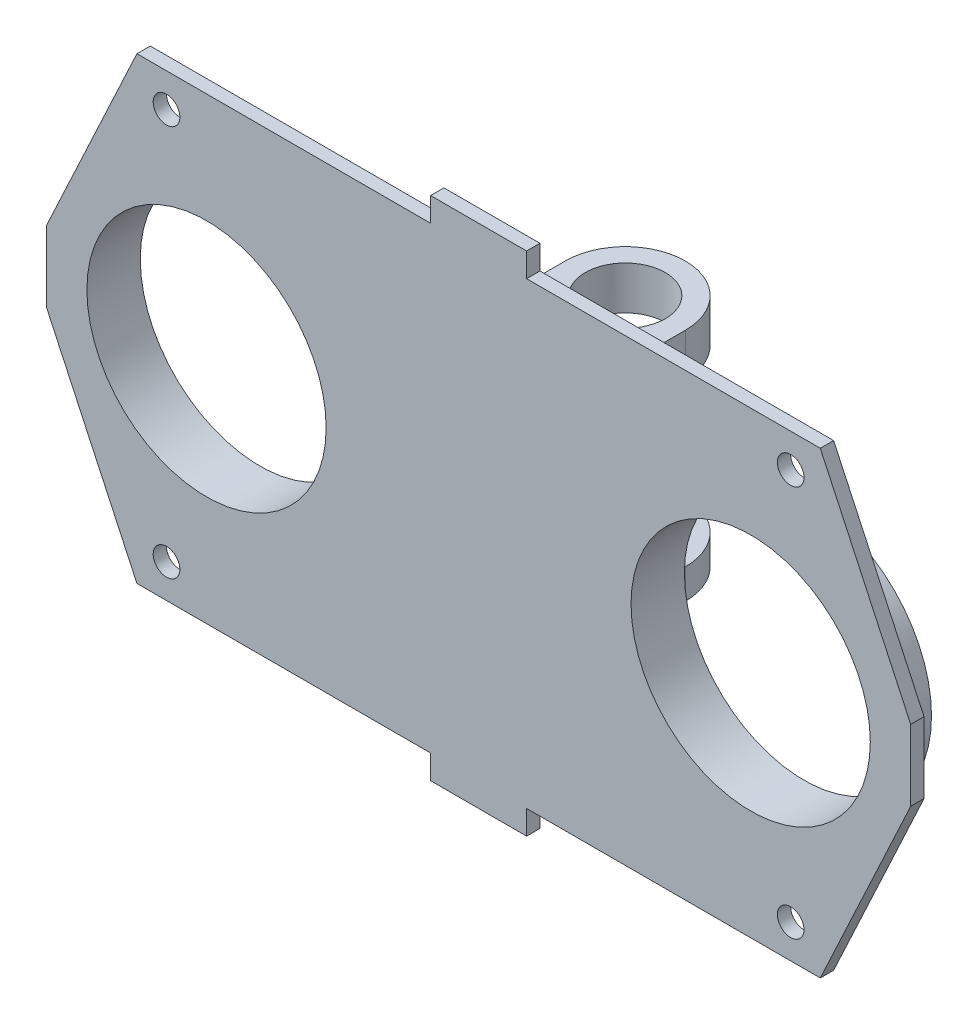
SolidWorks part; units mm, degrees
ref_plane "Front Plane" through (0, 0, 0) normal (0, 0, 1) x (1, 0, 0)
ref_plane "Top Plane" through (0, 0, 0) normal (0, 1, 0) x (1, 0, 0)
ref_plane "Right Plane" through (0, 0, 0) normal (1, 0, 0) x (0, 0, -1)
sketch "Sketch1" plane through (0, 0, 0) normal (0, 0, 1) x (1, 0, 0)
  line L0 (-219, 0) -> (219, 0) construction
  line L1 (0, 136.35) -> (0, -136.35) construction
  line L2 (-128.1, 86) -> (-18, 86)
  line L4 (-128.1, -86) -> (-18, -86)
  line L6 (-128.1, 86) -> (128.1, -86) construction
  line L7 (-128.1, -86) -> (128.1, 86) construction
  line L8 (18, 95) -> (-18, 95)
  line L9 (18, 95) -> (18, 86)
  line L10 (162, -13.3) -> (162, 13.3)
  line L13 (-83.3227, 44) -> (83.3227, 44)
  line L14 (-83.3227, -44) -> (83.3227, -44)
  line L15 (162, -13.3) -> (128.1, -86)
  line L16 (162, 13.3) -> (128.1, 86)
  line L17 (18, -95) -> (18, -86)
  line L18 (18, -95) -> (-18, -95)
  line L19 (-18, -95) -> (-18, -86)
  line L20 (-18, 95) -> (-18, 86)
  line L21 (-162, -13.3) -> (-128.1, -86)
  line L22 (-162, -13.3) -> (-162, 13.3)
  line L23 (-162, 13.3) -> (-128.1, 86)
  line L24 (18, 86) -> (128.1, 86)
  line L25 (18, -86) -> (128.1, -86)
  circle A0 centre (102, 0) radius 44.85
  circle A1 centre (102, 0) radius 47.8
  circle A2 centre (117, 73.4109) radius 5
  circle A3 centre (117, -73.4109) radius 5
  circle A4 centre (-117, -73.4109) radius 5
  circle A5 centre (-102, 0) radius 44.85
  circle A6 centre (-102, 0) radius 47.8
  circle A7 centre (-117, 73.4109) radius 5
  point P1 (0, 0)
  point P9 (0, 0)
  point P12 (0, 0)
  point P15 (0, 95)
  point P19 (162, 0)
  point P36 (0, -95)
  point P39 (0, 44)
  point P43 (0, -44)
  dimension "D8" = 95.6
  dimension "D9" = 162
  dimension "89.7" = 89.7
  dimension "D11" = 10
  dimension "D2" = 172
  dimension "D3" = 18
  dimension "D4" = 9
  dimension "D5" = 26.6
  dimension "D6" = 44
  dimension "D7" = 128.1
  dimension "D10" = 102
  dimension "D12" = 11.1
  dimension "D13" = 12.5891
  dimension "D14" = 128.1
extrude "Boss-Extrude3" add sketch "Sketch1" against normal blind 5 contours L17 L25 L15 L10 L16 L24 L9 L8 L20 L2 L23 L22 L21 L4 L19 L18 L14 A6 L13 A1 A3 A2 A4 A7 region at (-73.05, 82.244, 0)
extrude "Boss-Extrude4" add sketch "Sketch1<5>" against normal blind 10 contours L13 A6 L14 A1 region at (0, 0, 0)
sketch "Sketch1<5>" plane through (0, 0, 0) normal (0, 0, 1) x (1, 0, 0) same geometry as "Sketch1"
extrude "Boss-Extrude5" add sketch "Sketch1<6>" against normal blind 20 contours A1 A0 | A6 A5 region at (-63.2676, 25.6362, 0) region at (127.6362, 38.7324, 0)
sketch "Sketch1<6>" plane through (0, 0, 0) normal (0, 0, 1) x (1, 0, 0) same geometry as "Sketch1"
sketch "Sketch2" plane through (0, -44, 0) normal (0, -1, 0) x (1, 0, 0)
  line L0 (22.5, -55) -> (22.5, -10)
  line L1 (-83.3227, -10) -> (83.3227, -10) construction
  line L2 (-22.5, -10) -> (-22.5, -55)
  line L3 (-22.5, -10) -> (22.5, -10)
  arc A0 (-22.5, -55) -> (22.5, -55) centre (0, -55) ccw
  circle A1 centre (0, -55) radius 15
  dimension "D1" = 45
  dimension "D2" = 30
  dimension "D3" = 55
extrude "Boss-Extrude6" add sketch "Sketch2" against normal blind 88
sketch "Sketch3" plane through (-22.5, 0, 0) normal (-1, 0, 0) x (0, 0, 1)
  line L2 (-30, -32.8) -> (-120.1316, -32.8)
  line L3 (-120.1316, -32.8) -> (-120.1316, 27.7954)
  line L4 (-120.1316, 27.7954) -> (-30, 27.7954)
  line L5 (-30, 27.7954) -> (-30, -32.8)
extrude "Cut-Extrude1" cut sketch "Sketch3" against normal blind 57
